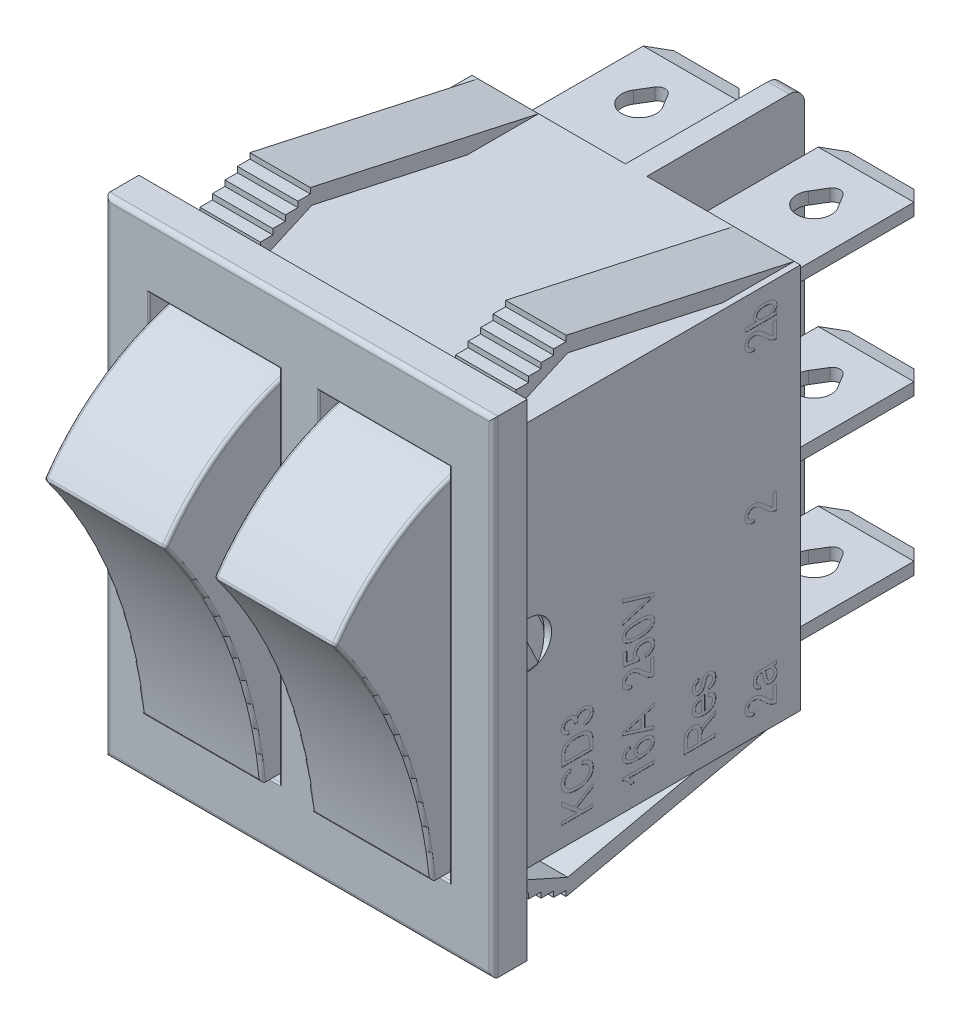
SolidWorks part; units mm, degrees
ref_plane "Спереди" through (0, 0, 0) normal (0, 0, 1) x (1, 0, 0)
ref_plane "Сверху" through (0, 0, 0) normal (0, 1, 0) x (1, 0, 0)
ref_plane "Справа" through (0, 0, 0) normal (1, 0, 0) x (0, 0, -1)
sketch "Эскиз1" plane through (0, 0, 0) normal (0, 0, 1) x (1, 0, 0)
  line L1 (10.725, 12.6) -> (-10.725, 12.6)
  line L2 (10.725, 12.6) -> (10.725, -12.6)
  line L3 (10.725, -12.6) -> (-10.725, -12.6)
  line L4 (-10.725, 12.6) -> (-10.725, -12.6)
  line L5 (10.725, 12.6) -> (-10.725, -12.6) construction
  line L6 (10.725, -12.6) -> (-10.725, 12.6) construction
  point P0 (0, 0)
  dimension "D1" = 21.45
  dimension "D2" = 25.2
extrude "Бобышка-Вытянуть1" add sketch "Эскиз1" along normal blind 32.3
sketch "Эскиз2" plane through (0, 0, 32.3) normal (0, 0, 1) x (1, 0, 0)
  line L1 (-12.675, 15.875) -> (12.675, 15.875)
  line L2 (-12.675, 15.875) -> (-12.675, -15.875)
  line L3 (-12.675, -15.875) -> (12.675, -15.875)
  line L4 (12.675, 15.875) -> (12.675, -15.875)
  line L5 (-12.675, 15.875) -> (12.675, -15.875) construction
  line L6 (-12.675, -15.875) -> (12.675, 15.875) construction
  point P0 (0, 0)
  dimension "D1" = 25.35
  dimension "D2" = 31.75
extrude "Бобышка-Вытянуть2" add sketch "Эскиз2" against normal blind 2.2
sketch "Эскиз3" plane through (0, 0, 0) normal (0, 0, -1) x (-1, 0, 0)
  line L0 (-10.725, 12.6) -> (10.725, 12.6) construction
  line L1 (0.7, 12.6) -> (10.725, 12.6)
  line L2 (0.7, 12.6) -> (0.7, -12.6)
  line L3 (0.7, -12.6) -> (10.725, -12.6)
  line L4 (10.725, 12.6) -> (10.725, -12.6)
  line L6 (-10.725, -12.6) -> (-0.7, -12.6)
  line L7 (-10.725, -12.6) -> (-10.725, 12.6)
  line L8 (-10.725, 12.6) -> (-0.7, 12.6)
  line L9 (-0.7, -12.6) -> (-0.7, 12.6)
  dimension "D1" = 1.4
extrude "Вырез-Вытянуть1" cut sketch "Эскиз3" against normal blind 10.3
sketch "Эскиз4" plane through (10.725, 0, 0) normal (1, 0, 0) x (0, 0, -1)
  line L0 (-14.9582, 12.6) -> (-25.0937, 14.8278)
  line L1 (-25.0937, 14.8278) -> (-30.1, 12.6)
  line L2 (-30.1, 12.6) -> (-10.3, 12.6) construction
  line L3 (-10.3, 12.6) -> (-25.2, 15.875)
  line L4 (-25.2, 15.875) -> (-30.1, 13.6945)
  line L5 (-30.1, -15.875) -> (-30.1, 15.875) construction
  line L6 (-30.1, 13.6945) -> (-30.1, 12.6)
  line L7 (-14.9582, 12.6) -> (-10.3, 12.6)
  line L8 (-20.2662, 13.7667) -> (-20.0515, 14.7434) construction
  line L9 (-27.3435, 13.8266) -> (-27.75, 14.7403) construction
  line L10 (-30.1, 0) -> (-16.1867, 0) construction
  line L11 (-30.1, -12.6) -> (-30.1, 12.6) construction
  dimension "D1" = 1
  dimension "D2" = 31.75
  dimension "D3" = 4.9
extrude "Бобышка-Вытянуть3" add sketch "Эскиз4" against normal blind 3.95 from offset 0.4 offset against normal yes
sketch "Эскиз5" plane through (10.325, 0, 0) normal (1, 0, 0) x (0, 0, -1)
  line L0 (-25.2, 15.875) -> (-25.2, 15.5116)
  line L1 (-25.2, 15.5116) -> (-26.0167, 15.5116)
  line L2 (-25.2, 15.875) -> (-30.1, 13.6945) construction
  line L3 (-26.0167, 15.5116) -> (-26.0167, 15.1482)
  line L4 (-26.0167, 15.1482) -> (-26.8333, 15.1482)
  line L5 (-26.8333, 15.1482) -> (-26.8333, 14.7848)
  line L6 (-26.8333, 14.7848) -> (-27.65, 14.7848)
  line L7 (-27.65, 14.7848) -> (-27.65, 14.4214)
  line L8 (-27.65, 14.4214) -> (-28.4667, 14.4214)
  line L9 (-28.4667, 14.4214) -> (-28.4667, 14.0579)
  line L10 (-28.4667, 14.0579) -> (-29.2833, 14.0579)
  line L11 (-29.2833, 14.0579) -> (-29.2833, 13.6945)
  line L12 (-29.2833, 13.6945) -> (-30.1, 13.6945)
  line L13 (-30.1, 13.6945) -> (-30.1, 12.6) construction
  line L14 (-30.1, 13.6945) -> (-30.1, 15.875)
  line L15 (-30.1, 15.875) -> (-25.2, 15.875)
extrude "Вырез-Вытянуть2" cut sketch "Эскиз5" against normal blind 3.95
pattern_linear "Линейный массив1" count 2 spacing 16.7 along (-1, 0, 0) of "Бобышка-Вытянуть3", "Вырез-Вытянуть2"
mirror "Зеркальное отражение1" about plane through (0, 0, 0) normal (0, 1, 0) of "Линейный массив1"
fillet "Скругление1" radius 1 2 edges at (0, -12.6, 0) (0, 12.6, 0)
sketch "Эскиз6" plane through (0, 0, 32.3) normal (0, 0, 1) x (1, 0, 0)
  line L0 (-5.55, 0) -> (5.55, 0) construction
  line L1 (12.675, -15.875) -> (12.675, 15.875) construction
  line L2 (-9.825, 11.75) -> (-1.275, 11.75)
  line L3 (-9.825, 11.75) -> (-9.825, -11.75)
  line L4 (-9.825, -11.75) -> (-1.275, -11.75)
  line L5 (-1.275, 11.75) -> (-1.275, -11.75)
  line L6 (-9.825, 11.75) -> (-1.275, -11.75) construction
  line L7 (-9.825, -11.75) -> (-1.275, 11.75) construction
  line L8 (1.275, 11.75) -> (9.825, 11.75)
  line L9 (1.275, 11.75) -> (1.275, -11.75)
  line L10 (1.275, -11.75) -> (9.825, -11.75)
  line L11 (9.825, 11.75) -> (9.825, -11.75)
  line L12 (1.275, 11.75) -> (9.825, -11.75) construction
  line L13 (1.275, -11.75) -> (9.825, 11.75) construction
  dimension "D1" = 8.55
  dimension "D2" = 23.5
  dimension "D3" = 2.85
extrude "Вырез-Вытянуть3" cut sketch "Эскиз6" against normal blind 5
sketch "Эскиз7" plane through (0, 0, 27.3) normal (0, 0, 1) x (1, 0, 0)
  line L0 (-9.825, 0) -> (-5.55, 0) construction
  line L1 (-9.825, 11.75) -> (-9.825, -11.75) construction
  line L2 (-5.55, 0) -> (-1.275, 0) construction
  line L3 (-1.275, -11.75) -> (-1.275, 11.75) construction
  line L4 (-1.275, 0) -> (1.275, 0) construction
  line L5 (1.275, 11.75) -> (1.275, -11.75) construction
  line L6 (1.275, 0) -> (5.55, 0) construction
  line L7 (5.55, 0) -> (9.825, 0) construction
  line L8 (9.825, -11.75) -> (9.825, 11.75) construction
  line L10 (-9.5, 11.5) -> (-1.6, 11.5)
  line L11 (-9.5, 11.5) -> (-9.5, -11.5)
  line L12 (-9.5, -11.5) -> (-1.6, -11.5)
  line L13 (-1.6, 11.5) -> (-1.6, -11.5)
  line L14 (-9.5, 11.5) -> (-1.6, -11.5) construction
  line L15 (-9.5, -11.5) -> (-1.6, 11.5) construction
  line L16 (1.6, 11.5) -> (9.5, 11.5)
  line L17 (1.6, 11.5) -> (1.6, -11.5)
  line L18 (1.6, -11.5) -> (9.5, -11.5)
  line L19 (9.5, 11.5) -> (9.5, -11.5)
  line L20 (1.6, 11.5) -> (9.5, -11.5) construction
  line L21 (1.6, -11.5) -> (9.5, 11.5) construction
  dimension "D1" = 7.9
  dimension "D2" = 23
extrude "Бобышка-Вытянуть4" add sketch "Эскиз7" along normal blind 12.2
sketch "Эскиз8" plane through (-9.5, 0, 0) normal (-1, 0, 0) x (0, 0, 1)
  line L0 (39.5, 11.5) -> (27.3, 11.5) construction
  line L1 (39.5, 11.5) -> (39.5, -11.5) construction
  line L2 (32.3, 15.875) -> (32.3, -15.875) construction
  line L3 (30.1, 15.875) -> (32.3, 15.875) construction
  line L4 (39.5, -11.5) -> (27.3, -11.5) construction
  line L5 (27.3, 11.5) -> (40.5, 11.5)
  line L6 (40.5, 11.5) -> (40.5, -11.5)
  line L7 (40.5, -11.5) -> (33.1, -11.5)
  arc A0 (27.3, 11.5) -> (39.5, 4.975) centre (27.3, -3.1679) cw
  arc A1 (39.5, 4.975) -> (33.1, -11.5) centre (65.937, -14.7755) ccw
  dimension "D4" = 33
  dimension "D1" = 5
  dimension "D2" = 10.9
  dimension "D3" = 0.8
  dimension "D5" = 1
extrude "Вырез-Вытянуть4" cut sketch "Эскиз8" against normal blind 7.9
pattern_linear "Линейный массив2" count 2 spacing 11.1 along (1, 0, 0) of "Вырез-Вытянуть4"
fillet "Скругление2" radius 0.1 8 edges at (5.55, -11.75, 32.3) (-5.55, -11.75, 32.3) (9.825, 0, 32.3) (1.275, 0, 32.3) (5.55, 11.75, 32.3) (-9.825, 0, 32.3) (-1.275, 0, 32.3) (-5.55, 11.75, 32.3)
fillet "Скругление3" radius 0.3 4 edges at (0, -15.875, 32.3) (12.675, 0, 32.3) (-12.675, 0, 32.3) (0, 15.875, 32.3)
fillet "Скругление4" radius 0.2 12 edges at (5.55, -11.5, 33.1) (-5.55, -11.5, 33.1) (9.5, 9.7663, 34.2177) (9.5, -2.8261, 35.1765) (5.55, 4.975, 39.5) (1.6, -2.8261, 35.1765) (1.6, 9.7663, 34.2177) (-1.6, 9.7663, 34.2177) (-1.6, -2.8261, 35.1765) (-5.55, 4.975, 39.5) (-9.5, 9.7663, 34.2177) (-9.5, -2.8261, 35.1765)
sketch "Эскиз9" plane through (-10.725, 0, 0) normal (-1, 0, 0) x (0, 0, 1)
  line L0 (0, 0) -> (28.05, 0) construction
  line L1 (32.3, 15.575) -> (32.3, -15.575) construction
  circle A0 centre (28.05, 0) radius 1.5
  circle A1 centre (28.05, 0) radius 1.45
  dimension "D1" = 3
  dimension "D3" = 2.9
  dimension "D2" = 4.25
extrude "Вырез-Вытянуть5" cut sketch "Эскиз9" against normal blind 0.5
sketch "Эскиз10" plane through (-10.725, 0, 0) normal (-1, 0, 0) x (0, 0, 1)
  line L0 (28.6628, 1.3141) -> (27.4372, -1.3141)
  line L1 (30.1, 12.6) -> (30.1, -12.6) construction
  circle A0 centre (28.05, 0) radius 1.45 construction
  arc A1 (28.6628, 1.3141) -> (27.4372, -1.3141) centre (28.05, 0) ccw
  point P4 (28.05, 0)
  dimension "D1" = 25
extrude "Вырез-Вытянуть6" cut sketch "Эскиз10" against normal blind 0.5
chamfer "Фаска1" distance 0.5 angle 70 1 edges at (-10.225, 0, 28.05) first distance on face at (-10.475, 0, 28.05)
mirror "Зеркальное отражение2" about plane through (0, 0, 0) normal (1, 0, 0) of "Вырез-Вытянуть5", "Вырез-Вытянуть6"
chamfer "Фаска5" distance 0.5 angle 70 1 edges at (10.225, 0, 28.05) first distance on face at (10.475, 0, 28.05)
sketch "Эскиз11" plane through (-10.725, 0, 0) normal (-1, 0, 0) x (0, 0, 1)
  line L0 (11.85, 11.5) -> (11.85, 0.6) construction
  line L1 (11.85, 0.6) -> (11.85, -9.1) construction
  line L2 (11.85, -9.1) -> (11.85, -14.0324) construction
  line L3 (10.3, -12.6) -> (10.3, 12.6) construction
  line L4 (0, 0) -> (11.1789, 0) construction
  line L5 (30.1, 12.6) -> (10.3, 12.6) construction
  line L6 (14.9582, -12.6) -> (10.3, -12.6) construction
  text T0 "1b"
  text T1 "1"
  text T2 "1a"
  dimension "D1" = 1.55
  dimension "D2" = 1.1
  dimension "D3" = 12
  dimension "D4" = 3.5
extrude "Вырез-Вытянуть7" cut sketch "Эскиз11" against normal blind 0.01
sketch "Эскиз12" plane through (10.725, 0, 0) normal (1, 0, 0) x (0, 0, -1)
  line L0 (-11.85, -11.5) -> (-11.85, -0.6) construction
  line L1 (-11.85, -0.6) -> (-11.85, 9.1) construction
  line L2 (-11.85, 9.1) -> (-11.85, 15.4527) construction
  line L3 (-10.3, -12.6) -> (-10.3, 12.6) construction
  line L4 (-30.1, 12.6) -> (-10.3, 12.6) construction
  line L5 (-30.1, -12.6) -> (-10.3, -12.6) construction
  line L6 (-11.85, -11.5) -> (-15.85, -11.5) construction
  line L7 (-15.85, -11.5) -> (-19.85, -11.5) construction
  line L8 (-19.85, -11.5) -> (-23.85, -11.5) construction
  line L9 (-23.85, -11.5) -> (-23.85, -2.7162) construction
  line L10 (-19.85, -11.5) -> (-19.85, 2.8692) construction
  line L11 (-15.85, -11.5) -> (-15.85, -3.4487) construction
  text T0 "2a"
  text T1 "2"
  text T2 "2b"
  text T3 "Res"
  text T4 "16A  250V"
  text T5 "KCD3"
  dimension "D1" = 1.55
  dimension "D2" = 3.5
  dimension "D3" = 1.1
  dimension "D4" = 12
  dimension "D5" = 4
extrude "Вырез-Вытянуть8" cut sketch "Эскиз12" against normal blind 0.01
sketch "Эскиз19" plane through (0, 0, 10.3) normal (0, 0, -1) x (-1, 0, 0)
  line L0 (-5.7125, 0) -> (5.7125, 0) construction
  line L1 (-5.7125, 10.15) -> (-5.7125, -10.15) construction
  line L2 (5.7125, 10.15) -> (5.7125, -10.15) construction
  line L3 (-5.7125, 10.15) -> (-5.7125, 14.0348) construction
  line L4 (-0.7, 14.0348) -> (-10.725, 14.0348) construction
  line L5 (-0.7, -11.6) -> (-0.7, 11.6) construction
  line L6 (-10.725, 12.6) -> (-10.725, -12.6) construction
  line L8 (-8.8375, 10.55) -> (-2.5875, 10.55)
  line L9 (-8.8375, 10.55) -> (-8.8375, 9.75)
  line L10 (-8.8375, 9.75) -> (-2.5875, 9.75)
  line L11 (-2.5875, 10.55) -> (-2.5875, 9.75)
  line L12 (-8.8375, 10.55) -> (-2.5875, 9.75) construction
  line L13 (-8.8375, 9.75) -> (-2.5875, 10.55) construction
  line L14 (-2.5875, 0.4) -> (-8.8375, 0.4)
  line L15 (-2.5875, 0.4) -> (-2.5875, -0.4)
  line L16 (-2.5875, -0.4) -> (-8.8375, -0.4)
  line L17 (-8.8375, 0.4) -> (-8.8375, -0.4)
  line L18 (-2.5875, 0.4) -> (-8.8375, -0.4) construction
  line L19 (-2.5875, -0.4) -> (-8.8375, 0.4) construction
  line L20 (-2.5875, -9.75) -> (-8.8375, -9.75)
  line L21 (-2.5875, -9.75) -> (-2.5875, -10.55)
  line L22 (-2.5875, -10.55) -> (-8.8375, -10.55)
  line L23 (-8.8375, -9.75) -> (-8.8375, -10.55)
  line L24 (-2.5875, -9.75) -> (-8.8375, -10.55) construction
  line L25 (-2.5875, -10.55) -> (-8.8375, -9.75) construction
  line L26 (2.5875, 10.55) -> (8.8375, 10.55)
  line L27 (2.5875, 10.55) -> (2.5875, 9.75)
  line L28 (2.5875, 9.75) -> (8.8375, 9.75)
  line L29 (8.8375, 10.55) -> (8.8375, 9.75)
  line L30 (2.5875, 10.55) -> (8.8375, 9.75) construction
  line L31 (2.5875, 9.75) -> (8.8375, 10.55) construction
  line L32 (2.5875, 0.4) -> (8.8375, 0.4)
  line L33 (2.5875, 0.4) -> (2.5875, -0.4)
  line L34 (2.5875, -0.4) -> (8.8375, -0.4)
  line L35 (8.8375, 0.4) -> (8.8375, -0.4)
  line L36 (2.5875, 0.4) -> (8.8375, -0.4) construction
  line L37 (2.5875, -0.4) -> (8.8375, 0.4) construction
  line L38 (2.5875, -9.75) -> (8.8375, -9.75)
  line L39 (2.5875, -9.75) -> (2.5875, -10.55)
  line L40 (2.5875, -10.55) -> (8.8375, -10.55)
  line L41 (8.8375, -9.75) -> (8.8375, -10.55)
  line L42 (2.5875, -9.75) -> (8.8375, -10.55) construction
  line L43 (2.5875, -10.55) -> (8.8375, -9.75) construction
  dimension "D1" = 0.8
  dimension "D2" = 6.25
  dimension "D3" = 21.1
extrude "Бобышка-Вытянуть5" add sketch "Эскиз19" along normal up to surface (10.3 mm away) up to face at (0, 0, 0)
chamfer "Фаска2" distance 1 angle 45 12 edges at (8.8375, 10.15, 0) (2.5875, 10.15, 0) (-8.8375, 10.15, 0) (-2.5875, 10.15, 0) (-8.8375, 0, 0) (-2.5875, 0, 0) (-8.8375, -10.15, 0) (-2.5875, -10.15, 0) (2.5875, -10.15, 0) (8.8375, -10.15, 0) (2.5875, 0, 0) (8.8375, 0, 0)
chamfer "Фаска3" distance 1 angle 15 6 edges at (-5.7125, -10.55, 0) (5.7125, -10.55, 0) (-5.7125, -0.4, 0) (5.7125, -0.4, 0) (-5.7125, 9.75, 0) (5.7125, 9.75, 0) first distance on face at (-5.7125, -10.55, 3.7667) first distance on face at (5.7125, -10.55, 3.7667) first distance on face at (-5.7125, -0.4, 3.7667) first distance on face at (5.7125, -0.4, 3.7667) first distance on face at (-5.7125, 9.75, 3.7667) first distance on face at (5.7125, 9.75, 3.7667)
chamfer "Фаска4" distance 1 angle 15 6 edges at (-5.7125, 10.55, 0) (5.7125, 10.55, 0) (5.7125, 0.4, 0) (-5.7125, 0.4, 0) (-5.7125, -9.75, 0) (5.7125, -9.75, 0) first distance on face at (-5.7125, 10.55, 3.7667) first distance on face at (5.7125, 10.55, 3.7667) first distance on face at (5.7125, 0.4, 3.7667) first distance on face at (-5.7125, 0.4, 3.7667) first distance on face at (-5.7125, -9.75, 3.7667) first distance on face at (5.7125, -9.75, 3.7667)
sketch "Эскиз20" plane through (0, -10.55, 0) normal (0, -1, 0) x (1, 0, 0)
  line L0 (0, 0) -> (0, 9) construction
  line L1 (-5.7125, 9) -> (5.7125, 9) construction
  line L2 (-5.7125, 4.4) -> (0, 4.4) construction
  line L3 (0, 4.4) -> (5.7125, 4.4) construction
  line L4 (-5.7125, 9) -> (-5.7125, 4.4) construction
  line L5 (-5.7125, 4.4) -> (-5.7125, 1) construction
  line L6 (-8.8375, 1) -> (-2.5875, 1) construction
  line L7 (6.375, 10.3) -> (0.7, 10.3) construction
  line L8 (7.8375, 0) -> (3.5875, 0) construction
  circle A0 centre (-5.7125, 9) radius 0.75
  circle A1 centre (5.7125, 9) radius 0.75
  circle A2 centre (-5.7125, 4.4) radius 1.125
  circle A3 centre (5.7125, 4.4) radius 1.125
  dimension "D1" = 1.5
  dimension "D2" = 2.25
  dimension "D4" = 4.4
  dimension "D3" = 1.3
extrude "Вырез-Вытянуть11" cut sketch "Эскиз20" against normal through all
sketch "Эскиз21" plane through (0, -10.55, 0) normal (0, -1, 0) x (1, 0, 0)
  line L0 (-6.6729, 3.8141) -> (-6.1393, 2.9396)
  line L1 (-4.7521, 3.8141) -> (-5.2857, 2.9396)
  line L2 (4.7521, 3.8141) -> (5.2857, 2.9396)
  line L3 (6.6729, 3.8141) -> (6.1393, 2.9396)
  line L4 (-5.7125, 3.2) -> (-5.7125, 4.4) construction
  line L5 (5.7125, 3.2) -> (5.7125, 4.4) construction
  circle A0 centre (-5.7125, 4.4) radius 1.125 construction
  circle A1 centre (5.7125, 4.4) radius 1.125 construction
  arc A2 (-6.1393, 2.9396) -> (-5.2857, 2.9396) centre (-5.7125, 3.2) ccw
  arc A3 (5.2857, 2.9396) -> (6.1393, 2.9396) centre (5.7125, 3.2) ccw
  arc A4 (-6.6729, 3.8141) -> (-4.7521, 3.8141) centre (-5.7125, 4.4) ccw
  arc A5 (4.7521, 3.8141) -> (6.6729, 3.8141) centre (5.7125, 4.4) ccw
  dimension "D1" = 0.5
  dimension "D2" = 1.2
extrude "Вырез-Вытянуть12" cut sketch "Эскиз21" against normal through all
sketch "Эскиз22" plane through (0, 0, 10.3) normal (0, 0, -1) x (-1, 0, 0)
  line L0 (-4.225, -8.1) -> (-4.225, -2.2354) construction
  line L1 (-10.725, 12.6) -> (-10.725, -12.6) construction
  line L2 (-6.375, -12.6) -> (-0.7, -12.6) construction
  text T0 "B1"
  dimension "D1" = 6.5
  dimension "D2" = 4.5
extrude "Бобышка-Вытянуть6" add sketch "Эскиз22" along normal blind 0.1
